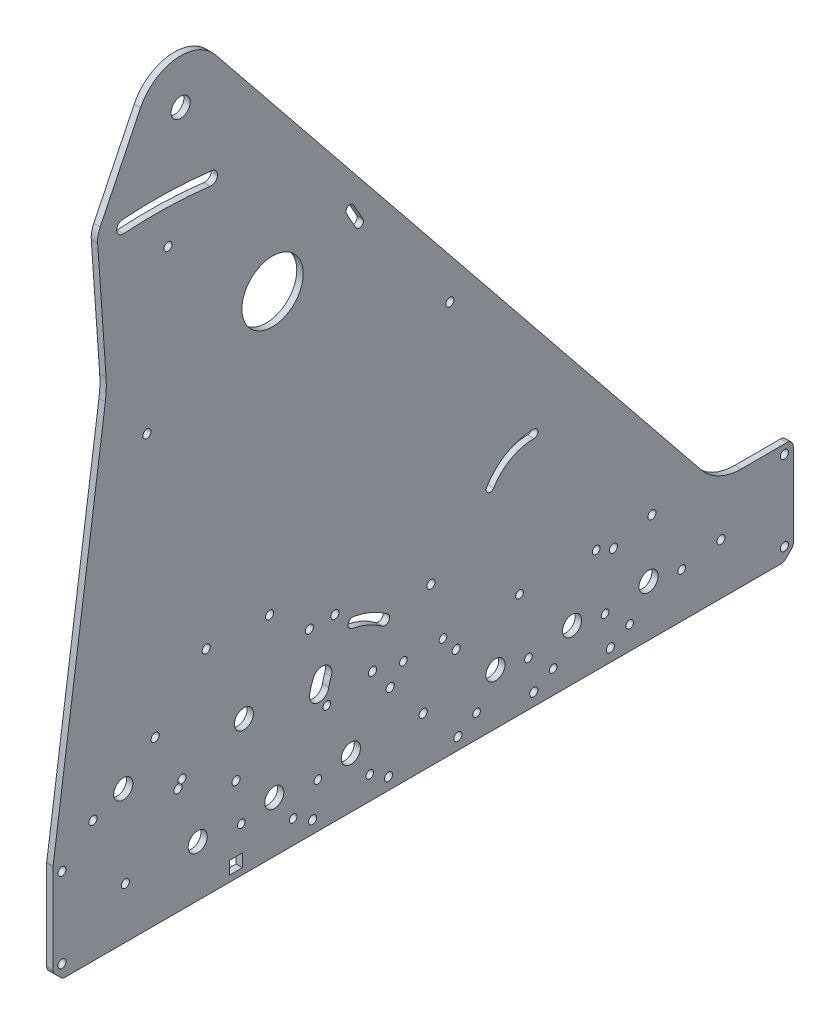
SolidWorks part; units mm, degrees
ref_plane "Front Plane" through (0, 0, 0) normal (0, 0, 1) x (1, 0, 0)
ref_plane "Top Plane" through (0, 0, 0) normal (0, 1, 0) x (1, 0, 0)
ref_plane "Right Plane" through (0, 0, 0) normal (1, 0, 0) x (0, 0, -1)
sketch "Sketch1" plane through (0, 0, 0) normal (1, 0, 0) x (0, 0, -1)
  line L0 (-184.15, -24.6062) -> (184.15, -24.6062)
  line L1 (184.15, -24.6062) -> (184.15, 26.1938)
  line L2 (184.15, 26.1938) -> (146.05, 26.1937)
  line L5 (-142.6632, 324.5299) -> (-184.15, 26.1938)
  line L6 (-184.15, 26.1938) -> (-184.15, -24.6062)
  line L7 (-184.15, 350.0437) -> (184.15, 350.0437) construction
  line L9 (146.05, 26.1937) -> (-103.3504, 335.4213)
  arc A0 (-103.3504, 335.4213) -> (-142.6632, 324.5299) centre (-120.65, 321.4687) ccw
  point P8 (0, -24.6062)
  dimension "D1" = 368.3
  dimension "D7" = 44.45
  dimension "D2" = 50.8
  dimension "D3" = 38.1
  dimension "D4" = 24.6062
  dimension "D5" = 374.65
  dimension "D6" = 304.8
  dimension "D8" = 346.075
extrude "Boss-Extrude1" add sketch "Sketch1" along normal blind 3.175
chamfer "Chamfer1" distance 4.7625 angle 45 2 edges at (1.5875, -24.6062, 184.15) (1.5875, -24.6062, -184.15)
fillet "Fillet1" radius 25.4 1 edges at (1.5875, 26.1937, -146.05)
fillet "Fillet2" radius 3.175 2 edges at (1.5875, 26.1938, 184.15) (1.5875, 26.1938, -184.15)
fillet "Fillet3" radius 3.175 4 edges at (1.5875, -19.8438, -184.15) (1.5875, -24.6062, -179.3875) (1.5875, -19.8437, 184.15) (1.5875, -24.6062, 179.3875)
sketch "Sketch30" plane through (3.175, 0, 0) normal (1, 0, 0) x (0, 0, -1)
  circle A8 centre (-89.211, 42.2593) radius 4.7625
  circle A9 centre (-25.1593, 30.6938) radius 2.032
  arc A10 (-51.7173, 35.4892) -> (-50.2741, 40.5715) centre (-25.1593, 30.6938) cw construction
  arc A11 (-54.7652, 42.3379) -> (-56.4665, 36.3468) centre (-25.1593, 30.6938) ccw
  arc A12 (-45.783, 38.8051) -> (-46.9681, 34.6317) centre (-25.1593, 30.6938) ccw
  arc A13 (-45.783, 38.8051) -> (-54.7652, 42.3379) centre (-50.2741, 40.5715) ccw
  arc A14 (-56.4665, 36.3468) -> (-46.9681, 34.6317) centre (-51.7173, 35.4892) ccw
  arc A15 (-34.9881, 56.6661) -> (-19.1131, 49.8125) centre (-41.7582, 19.1724) cw construction
  arc A16 (-17.6789, 51.753) -> (-34.5594, 59.0407) centre (-41.7582, 19.1724) ccw
  arc A17 (-20.5473, 47.8719) -> (-35.4169, 54.2915) centre (-41.7582, 19.1724) ccw
  arc A18 (-20.5473, 47.8719) -> (-17.6789, 51.753) centre (-19.1131, 49.8125) ccw
  arc A19 (-34.5594, 59.0407) -> (-35.4169, 54.2915) centre (-34.9881, 56.6661) ccw
  arc A20 (-19.1131, 49.8125) -> (-34.9881, 56.6661) centre (-41.7582, 19.1724) ccw construction
  circle A21 centre (94.6345, 23.8125) radius 2.032
  circle A22 centre (-56.6241, 64.5541) radius 2.032
  circle A23 centre (-43.9241, 64.5541) radius 2.032
  circle A24 centre (-56.6241, 64.5541) radius 1.905 construction
  circle A25 centre (-43.9241, 64.5541) radius 1.905 construction
  point P7 (-51.1204, 38.0658)
  point P19 (-26.6567, 54.1518)
  dimension "D2" = 9.652
  dimension "D4" = 4.064
  dimension "D1" = 4.064
  dimension ".375" = 9.525
  dimension "D3" = 4.826
extrude "Cut-Extrude9" cut sketch "Sketch30" against normal through all
sketch "Sketch16" plane through (3.175, 0, 0) normal (1, 0, 0) x (0, 0, -1)
  circle A0 centre (112.1746, 0.7937) radius 4.7625
  circle A1 centre (74.0746, 0.7937) radius 4.7625
  circle A2 centre (35.9746, 0.7937) radius 4.7625
  circle A3 centre (-35.9746, 0.7938) radius 4.7625
  circle A4 centre (-74.0746, 0.7938) radius 4.7625
  circle A5 centre (-112.1746, 0.7937) radius 4.7625
  dimension "D1" = 9.525
  dimension "D2" = 9.525
extrude "Cut-Extrude1" cut sketch "Sketch16" against normal up to next
sketch "Sketch25" plane through (3.175, 0, 0) normal (1, 0, 0) x (0, 0, -1)
  circle A0 centre (102.7672, -13.0003) radius 1.905 construction
  circle A1 centre (86.0486, 27.3622) radius 1.905 construction
  circle A2 centre (128.5804, -2.3081) radius 1.905 construction
  circle A3 centre (102.7672, -13.0003) radius 1.905
  circle A4 centre (86.0486, 27.3622) radius 1.905
  circle A5 centre (128.5804, -2.3081) radius 1.905
  circle A6 centre (64.6672, -13.0003) radius 1.905 construction
  circle A8 centre (-9.8486, 27.3622) radius 1.905 construction
  circle A10 centre (-47.9486, 27.3622) radius 1.905 construction
  circle A11 centre (-90.4804, -2.3081) radius 1.905 construction
  circle A12 centre (-64.6672, -13.0003) radius 1.905 construction
  circle A14 centre (-52.3804, -2.3081) radius 1.905 construction
  circle A15 centre (-26.5672, -13.0003) radius 1.905 construction
  circle A16 centre (9.8486, 27.3622) radius 1.905 construction
  circle A17 centre (26.5672, -13.0003) radius 1.905 construction
  circle A18 centre (47.9486, 27.3622) radius 1.905 construction
  circle A19 centre (52.3804, -2.3081) radius 1.905 construction
  circle A20 centre (90.4804, -2.3081) radius 1.905 construction
  circle A21 centre (-9.8486, 27.3622) radius 1.905
  circle A23 centre (-47.9486, 27.3622) radius 1.905
  circle A24 centre (-90.4804, -2.3081) radius 1.905
  circle A25 centre (-64.6672, -13.0003) radius 1.905
  circle A27 centre (-52.3804, -2.3081) radius 1.905
  circle A28 centre (-26.5672, -13.0003) radius 1.905
  circle A29 centre (9.8486, 27.3622) radius 1.905
  circle A30 centre (26.5672, -13.0003) radius 1.905
  circle A31 centre (47.9486, 27.3622) radius 1.905
  circle A32 centre (64.6672, -13.0003) radius 1.905
  circle A33 centre (52.3804, -2.3081) radius 1.905
  circle A34 centre (90.4804, -2.3081) radius 1.905
extrude "Cut-Extrude4" cut sketch "Sketch25" against normal up to next
sketch "Sketch23" plane through (3.175, 0, 0) normal (1, 0, 0) x (0, 0, -1)
  circle A0 centre (179.705, 21.7488) radius 1.905 construction
  point P0 (-55.0246, -18.3223)
  point P6 (-93.1246, 17.5943)
  point P9 (-17.2515, -18.6426)
  point P12 (-16.4124, 19.3854)
  point P15 (16.4124, 19.3854)
  point P18 (17.2515, -18.6426)
  point P21 (55.0246, -18.3223)
  point P35 (3.8736, 53.6853)
  point P38 (113.7728, 28.6594)
  point P44 (-179.705, 21.7487)
  point P47 (-179.705, -18.0026)
  point P50 (179.705, 21.7488)
  point P53 (179.705, -18.0026)
  point P59 (93.1246, -18.3223)
  point P63 (-122.0103, 28.5049)
  point P66 (-164.29, 36.0603)
hole_wizard "#8 (0.16) Diameter Hole1" positions "Sketch23" profile "Sketch24" hole size "#8" standard "ANSI Inch" end condition up to next
sketch "Sketch24" plane through (3.175, -18.3223, 55.0246) normal (0, 1, 0) x (0, 0, -1)
  line L0 (0, 0) -> (0, 3.175)
  line L1 (0, 3.175) -> (2.032, 3.175)
  line L2 (2.032, 3.175) -> (2.032, 0)
  line L5 (2.032, 0) -> (0, 0)
  line L11 (0, -6.35) -> (0, 107.95) construction
  dimension "Thru Hole Dia." = 4.064
  dimension "Thru Hole Depth" = 3.175
sketch "Sketch22" plane through (3.175, 0, 0) normal (1, 0, 0) x (0, 0, -1)
  line L0 (-96.2996, -15.1473) -> (-89.9496, -15.1473) construction
  line L1 (-96.2996, -15.1473) -> (-89.9496, -15.1473)
  line L2 (-96.2996, -15.1473) -> (-96.2996, -21.4973)
  line L3 (-96.2996, -21.4973) -> (-89.9496, -21.4973)
  line L4 (-89.9496, -15.1473) -> (-89.9496, -21.4973)
  line L5 (-96.2996, -15.1473) -> (-89.9496, -21.4973) construction
  line L6 (-96.2996, -21.4973) -> (-89.9496, -15.1473) construction
  line L7 (-89.9496, -15.1473) -> (-89.9496, -19.8734) construction
  point P0 (-93.1246, -18.3223)
  dimension "D1" = 6.35
extrude "Cut-Extrude3" cut sketch "Sketch22" against normal up to next
sketch "Sketch21" plane through (3.175, 0, 0) normal (1, 0, 0) x (0, 0, -1)
  circle A0 centre (-148.1579, 0.7937) radius 2.032
  circle A2 centre (0, 0) radius 2.032
  circle A3 centre (148.1579, 0.7938) radius 2.032
  dimension "D1" = 4.064
extrude "Cut-Extrude2" cut sketch "Sketch21" against normal up to next
sketch "Sketch26" [suppressed] plane through (3.175, 0, 0) normal (1, 0, 0) x (0, 0, -1)
  line L0 (-145.839, 321.5609) -> (-184.1236, 26.3971) construction
  line L1 (-178.0724, -24.6062) -> (178.0724, -24.6062) construction
  circle A0 centre (-121.0218, 216.6937) radius 15.24
  dimension "D1" = 30.48
  dimension "D2" = 38.1
  dimension "D3" = 241.3
extrude "Cut-Extrude5" [suppressed] cut sketch "Sketch26" against normal through all
sketch "Sketch27" plane through (3.175, 0, 0) normal (1, 0, 0) x (0, 0, -1)
  circle A0 centre (-120.65, 321.4687) radius 4.7625
  dimension "D1" = 9.525
extrude "Cut-Extrude6" cut sketch "Sketch27" against normal through all
sketch "Sketch28" plane through (3.175, 0, 0) normal (1, 0, 0) x (0, 0, -1)
  line L0 (-120.65, 321.4687) -> (-103.9389, 280.2796) construction
  line L1 (-103.9389, 280.2796) -> (-86.9156, 261.4285) construction
  line L2 (-86.9156, 261.4285) -> (-90.8226, 249.3444) construction
  line L3 (-90.8226, 249.3444) -> (-94.7296, 237.2603) construction
  line L4 (-142.6632, 324.5299) -> (-184.1197, 26.4114) construction
  circle A0 centre (-94.7296, 237.2603) radius 2.032
  circle A1 centre (-90.8226, 249.3444) radius 2.032
  circle A2 centre (-86.9156, 261.4285) radius 2.0955
  circle A3 centre (-103.9389, 280.2796) radius 2.032
  dimension "D4" = 4.064
  dimension "D5" = 4.191
  dimension "D6" = 4.064
  dimension "D1" = 25.4
  dimension "D2" = 44.45
  dimension "D3" = 12.7
  dimension "D7" = 30
  dimension "D8" = 120
  dimension "D9" = 160
extrude "Cut-Extrude7" [suppressed] cut sketch "Sketch28" against normal through all
sketch "Sketch31" plane through (0, 0, 0) normal (-1, 0, 0) x (0, 0, 1)
extrude "Cut-Extrude10" [suppressed] cut sketch "Sketch31" against normal through all
sketch "Sketch34" plane through (0, 0, 0) normal (-1, 0, 0) x (0, 0, 1)
  line L3 (123.2042, 95.6381) -> (126.7027, 70.4802) construction
  line L4 (125.3426, 95.9355) -> (128.8411, 70.7775)
  line L5 (121.0658, 95.3407) -> (124.5642, 70.1828)
  line L6 (142.6632, 324.5299) -> (184.1197, 26.4114) construction
  arc A2 (125.3426, 95.9355) -> (121.0658, 95.3407) centre (123.2042, 95.6381) ccw
  arc A3 (124.5642, 70.1828) -> (128.8411, 70.7775) centre (126.7027, 70.4802) ccw
  point P9 (124.9534, 83.0591)
  dimension "D8" = 4.318
  dimension "D6" = 50.8
  dimension "D7" = 25.4
extrude "Cut-Extrude12" [suppressed] cut sketch "Sketch34" against normal through all
sketch "Sketch38" plane through (3.175, 0, 0) normal (1, 0, 0) x (0, 0, -1)
  line L0 (-184.15, 25.974) -> (-184.15, -18.5286) construction
  line L1 (-178.0724, -24.6062) -> (178.0724, -24.6062) construction
  circle A0 centre (-133.35, 56.3562) radius 2.032
  circle A1 centre (-149.225, 42.0687) radius 4.7625
  circle A2 centre (-107.95, 81.7563) radius 2.032
  dimension "D1" = 50.8
  dimension "D3" = 4.064
  dimension "D4" = 9.525
  dimension "D7" = 4.064
  dimension "D2" = 80.9625
  dimension "D5" = 15.875
  dimension "D6" = 14.2875
  dimension "D8" = 25.4
  dimension "D9" = 25.4
extrude "Cut-Extrude14" cut sketch "Sketch38" against normal through all
sketch "Sketch56" plane through (3.175, 0, 0) normal (1, 0, 0) x (0, 0, -1)
  line L0 (-133.35, 284.9563) -> (-133.35, 56.3562) construction
  line L1 (-149.2963, 284.3994) -> (-133.35, 56.3562) construction
  line L2 (-133.35, 56.3562) -> (-105.4907, 283.2523) construction
  arc A0 (-149.2963, 284.3994) -> (-105.4907, 283.2523) centre (-133.35, 56.3562) cw
  arc A1 (-142.7671, 191.0274) -> (-116.8976, 190.35) centre (-133.35, 56.3562) cw
  dimension "D1" = 4
  dimension "D3" = 228.6
  dimension "D4" = 135
  dimension "D2" = 7
sketch "Sketch54" plane through (3.175, 0, 0) normal (1, 0, 0) x (0, 0, -1)
  line L0 (-142.6632, 324.5299) -> (-184.1197, 26.4114) construction
  line L1 (-140.6316, 331.1994) -> (-160.7144, 289.9597)
  line L2 (-142.6632, 324.5299) -> (-157.4154, 218.4453)
  line L3 (-140.6316, 331.1994) -> (-217.348, 331.1994) construction
  line L4 (-149.2963, 284.3994) -> (-133.35, 56.3562) construction
  line L5 (-161.9654, 283.5135) -> (-157.4154, 218.4453)
  arc A1 (-103.3504, 335.4213) -> (-142.6632, 324.5299) centre (-120.65, 321.4687) ccw construction
  arc A2 (-160.7144, 289.9597) -> (-161.9654, 283.5135) centre (-149.2963, 284.3994) ccw
  arc A3 (-140.6316, 331.1994) -> (-142.6632, 324.5299) centre (-120.65, 321.4687) ccw
  dimension "D1" = 12.7
extrude "Boss-Extrude2" add sketch "Sketch54" against normal up to surface (3.175 mm away) up to face at (0, 81.7563, 105.918)
sketch "Sketch57" plane through (3.175, 0, 0) normal (1, 0, 0) x (0, 0, -1)
  line L0 (138.4249, 35.6479) -> (-103.3504, 335.4213) construction
  arc A0 (-149.2963, 284.3994) -> (-105.4907, 283.2523) centre (-133.35, 56.3562) cw construction
  arc A1 (-105.1037, 286.4036) -> (-149.5178, 287.5667) centre (-133.35, 56.3562) ccw
  arc A2 (-105.8776, 280.101) -> (-149.0749, 281.2321) centre (-133.35, 56.3562) ccw
  arc A3 (-105.8776, 280.101) -> (-105.1037, 286.4036) centre (-105.4907, 283.2523) ccw
  arc A4 (-149.5178, 287.5667) -> (-149.0749, 281.2321) centre (-149.2963, 284.3994) ccw
  arc A5 (-105.4907, 283.2523) -> (-149.2963, 284.3994) centre (-133.35, 56.3562) ccw construction
  arc A6 (-142.7671, 191.0274) -> (-116.8976, 190.35) centre (-133.35, 56.3562) cw construction
  arc A7 (-116.5107, 193.5013) -> (-142.9886, 194.1947) centre (-133.35, 56.3562) ccw construction
  arc A8 (-117.2846, 187.1986) -> (-142.5456, 187.8601) centre (-133.35, 56.3562) ccw construction
  arc A9 (-117.2846, 187.1986) -> (-116.5107, 193.5013) centre (-116.8976, 190.35) ccw construction
  arc A10 (-142.9886, 194.1947) -> (-142.5456, 187.8601) centre (-142.7671, 191.0274) ccw construction
  circle A11 centre (13.2774, 170.5867) radius 2.032
  point P3 (-127.3659, 284.8779)
  point P16 (-129.8161, 191.31)
  dimension "D1" = 6.35
  dimension "D2" = 4.064
  dimension "D3" = 12.7
  dimension "D4" = 130.175
extrude "Cut-Extrude26" cut sketch "Sketch57" against normal up to next
sketch "Sketch37" plane through (3.175, 0, 0) normal (1, 0, 0) x (0, 0, -1)
  line L0 (55.0742, 92.9044) -> (63.2984, 92.9044) construction
  arc A1 (33.3375, 80.645) -> (55.0742, 92.9044) centre (55.0742, 67.5044) cw construction
  arc A2 (55.0742, 94.9364) -> (31.5986, 81.6962) centre (55.0742, 67.5044) ccw
  arc A3 (55.0742, 90.8724) -> (35.0764, 79.5938) centre (55.0742, 67.5044) ccw
  arc A4 (55.0742, 90.8724) -> (55.0742, 94.9364) centre (55.0742, 92.9044) ccw
  arc A5 (31.5986, 81.6962) -> (35.0764, 79.5938) centre (33.3375, 80.645) ccw
  circle A8 centre (0, 0) radius 2.032 construction
  point P4 (42.5965, 89.6283)
  dimension "D1" = 25.4
  dimension "D4" = 24.9555
  dimension "D5" = 2.032
  dimension "D2" = 33.3375
  dimension "D3" = 80.645
extrude "Cut-Extrude13" cut sketch "Sketch37" against normal through all
sketch "Sketch40" plane through (3.175, 0, 0) normal (1, 0, 0) x (0, 0, -1)
  circle A0 centre (-120.015, 31.75) radius 2.032
  dimension "D1" = 4.064
  dimension "D2" = 120.015
  dimension "D3" = 31.75
extrude "Cut-Extrude16" cut sketch "Sketch40" against normal through all
sketch "Sketch41" [suppressed] plane through (3.175, 0, 0) normal (1, 0, 0) x (0, 0, -1)
  line L0 (-120.65, 318.2937) -> (-98.425, 279.7989) construction
  line L1 (-98.425, 279.7989) -> (-77.6666, 265.1617) construction
  line L2 (-120.65, 318.2937) -> (-60.41, 318.2937) construction
  circle A0 centre (-120.65, 318.2937) radius 25.4 construction
  circle A1 centre (-98.425, 279.7989) radius 19.05 construction
  circle A2 centre (-77.6666, 265.1617) radius 6.35 construction
  circle A3 centre (-98.425, 279.7989) radius 2.032
  circle A4 centre (-77.6666, 265.1617) radius 2.032
  dimension "D1" = 50.8
  dimension "D2" = 38.1
  dimension "D3" = 12.7
  dimension "D4" = 4.064
  dimension "D5" = 60
extrude "Cut-Extrude17" [suppressed] cut sketch "Sketch41" against normal through all
sketch "Sketch43" plane through (3.175, 0, 0) normal (1, 0, 0) x (0, 0, -1)
  line L0 (-152.4, 200.025) -> (-123.6487, 200.025) construction
  line L1 (-115.9779, 252.0412) -> (-152.4, 200.025) construction
  circle A0 centre (-152.4, 200.025) radius 2.032
  arc A1 (-143.2813, 262.8669) -> (-96.4668, 230.087) centre (-152.4, 200.025) cw construction
  arc A2 (-92.2158, 232.3717) -> (-142.5883, 267.6428) centre (-152.4, 200.025) ccw
  arc A3 (-100.7177, 227.8023) -> (-143.9743, 258.0909) centre (-152.4, 200.025) ccw
  arc A4 (-100.7177, 227.8023) -> (-92.2158, 232.3717) centre (-96.4668, 230.087) ccw
  arc A5 (-142.5883, 267.6428) -> (-143.9743, 258.0909) centre (-143.2813, 262.8669) ccw
  point P6 (-115.9779, 252.0412)
  dimension "D1" = 4.064
  dimension "D4" = 4.826
  dimension "D2" = 200.025
  dimension "D3" = 152.4
  dimension "D5" = 63.5
  dimension "D6" = 57.15
  dimension "D7" = 55
extrude "Cut-Extrude19" [suppressed] cut sketch "Sketch43" against normal through all
sketch "Sketch44" plane through (3.175, 0, 0) normal (1, 0, 0) x (0, 0, -1)
  circle A0 centre (-142.875, 226.3775) radius 2.032
  dimension "D1" = 4.064
  dimension "D2" = 142.875
  dimension "D3" = 226.3775
extrude "Cut-Extrude20" [suppressed] cut sketch "Sketch44" against normal through all
sketch "Sketch50" plane through (0, 0, 0) normal (-1, 0, 0) x (0, 0, 1)
  line L0 (89.6567, 207.1688) -> (64.2567, 207.1688) construction
  line L1 (89.6567, 205.1368) -> (64.2567, 205.1368)
  line L2 (89.6567, 209.2008) -> (64.2567, 209.2008)
  line L3 (64.2567, 194.4688) -> (38.8567, 194.4688) construction
  line L4 (64.2567, 192.4368) -> (38.8567, 192.4368)
  line L5 (64.2567, 196.5008) -> (38.8567, 196.5008)
  arc A1 (89.6567, 205.1368) -> (89.6567, 209.2008) centre (89.6567, 207.1688) ccw
  arc A2 (64.2567, 209.2008) -> (64.2567, 205.1368) centre (64.2567, 207.1688) ccw
  arc A3 (64.2567, 192.4368) -> (64.2567, 196.5008) centre (64.2567, 194.4688) ccw
  arc A4 (38.8567, 196.5008) -> (38.8567, 192.4368) centre (38.8567, 194.4688) ccw
  point P3 (76.9567, 207.1688)
  point P5 (51.5567, 194.4688)
  dimension "D1" = 2.032
  dimension "D2" = 207.1688
  dimension "D3" = 89.6567
  dimension "D4" = 25.4
  dimension "D5" = 12.7
extrude "Cut-Extrude22" [suppressed] cut sketch "Sketch50" against normal through all
sketch "Sketch51" plane through (3.175, 0, 0) normal (1, 0, 0) x (0, 0, -1)
  circle A0 centre (-111.125, 222.6469) radius 2.032
  circle A1 centre (-111.125, 190.8969) radius 2.032
  dimension "D1" = 222.6469
  dimension "D3" = 31.75
  dimension "D4" = 4.064
  dimension "D2" = 111.125
extrude "Cut-Extrude23" [suppressed] cut sketch "Sketch51" against normal through all
sketch "Sketch52" [suppressed] plane through (0, 0, 0) normal (-1, 0, 0) x (0, 0, 1)
  line L0 (145.839, 321.5609) -> (184.1236, 26.3971) construction
  line L1 (142.875, 226.3775) -> (142.0856, 251.7652) construction
  line L2 (120.4939, 238.3877) -> (142.875, 226.3775) construction
  arc A5 (142.0856, 251.7652) -> (120.4939, 238.3877) centre (142.875, 226.3775) ccw construction
  arc A6 (142.0224, 253.7962) -> (118.7034, 239.3485) centre (142.875, 226.3775) ccw
  arc A7 (142.1487, 249.7342) -> (122.2844, 237.4269) centre (142.875, 226.3775) ccw
  arc A8 (142.1487, 249.7342) -> (142.0224, 253.7962) centre (142.0856, 251.7652) ccw
  arc A9 (118.7034, 239.3485) -> (122.2844, 237.4269) centre (120.4939, 238.3877) ccw
  point P4 (129.4975, 247.9692)
  dimension "D1" = 25.4
  dimension "D2" = 2.032
  dimension "D3" = 12.7
  dimension "D4" = 60
extrude "Cut-Extrude24" [suppressed] cut sketch "Sketch52" against normal through all
sketch "Sketch53" plane through (3.175, 0, 0) normal (1, 0, 0) x (0, 0, -1)
  line L0 (-25.4, 197.2663) -> (-25.4, 135.876) construction
  line L1 (-23.368, 197.2663) -> (-23.368, 135.876)
  line L2 (-27.432, 197.2663) -> (-27.432, 135.876)
  arc A0 (-23.368, 197.2663) -> (-27.432, 197.2663) centre (-25.4, 197.2663) ccw
  arc A1 (-27.432, 135.876) -> (-23.368, 135.876) centre (-25.4, 135.876) ccw
  point P2 (-25.4, 166.5712)
  dimension "D1" = 2.032
  dimension "D2" = 61.3903
  dimension "D3" = 197.2663
  dimension "D4" = 25.4
extrude "Cut-Extrude25" [suppressed] cut sketch "Sketch53" against normal through all
sketch "Sketch58" plane through (3.175, 0, 0) normal (1, 0, 0) x (0, 0, -1)
  line L0 (138.4249, 35.6479) -> (-103.3504, 335.4213) construction
  line L1 (-74.9571, 219.298) -> (-112.7732, 223.9412) construction
  line L2 (-133.35, 56.3562) -> (-105.4907, 283.2523) construction
  circle A0 centre (-74.9571, 219.298) radius 15.24
  dimension "D1" = 50.8
  dimension "D2" = 30.48
  dimension "D3" = 38.1
extrude "Cut-Extrude27" cut sketch "Sketch58" against normal through all
sketch "Sketch60" [suppressed] plane through (0, 0, 0) normal (-1, 0, 0) x (0, 0, 1)
  line L1 (-37.547, 154.5028) -> (64.3989, 263.8478) construction
  line L2 (120.65, 321.4687) -> (120.65, 283.4951) construction
  line L3 (-17.6374, 138.8786) -> (63.8163, 263.1055) construction
  line L4 (113.0282, 299.2883) -> (107.0925, 303.8578) construction
  line L5 (65.8258, 264.9495) -> (112.2759, 289.9949) construction
  line L7 (120.65, 321.4687) -> (120.65, 359.4144) construction
  line L8 (120.65, 321.4687) -> (109.6389, 294.8856) construction
  line L10 (120.65, 321.4687) -> (-169.232, 227.2804) construction
  line L11 (120.65, 321.4687) -> (354.1403, 125.5471) construction
  line L12 (64.8747, 264.3011) -> (106.0507, 299.1279) construction
  line L13 (110.3554, 300.3954) -> (117.7837, 299.4293) construction
  line L14 (-16.0993, 160.9177) -> (-13.2774, 170.5867) construction
  circle A7 centre (74.9571, 219.298) radius 33.3375 construction
  circle A10 centre (68.4628, 260.0588) radius 2.032
  circle A11 centre (68.4628, 260.0588) radius 7.9375 construction
  circle A15 centre (-28.258, 145.8423) radius 1.778
  circle A17 centre (120.65, 321.4687) radius 22.225 construction
  circle A20 centre (109.6389, 294.8856) radius 6.5484 construction
  circle A21 centre (109.6389, 294.8856) radius 2.032
  circle A22 centre (109.6389, 294.8856) radius 5.5563 construction
  circle A23 centre (68.4628, 260.0588) radius 5.5563 construction
  circle A24 centre (-28.258, 145.8423) radius 12.7 construction
  arc A25 (-44.7806, 147.1408) -> (-23.4901, 129.9695) centre (-28.258, 145.8423) ccw construction
  circle A26 centre (-16.0993, 160.9177) radius 2.032
  circle A27 centre (-35.0103, 118.6566) radius 2.032
  circle A28 centre (-53.3973, 133.4862) radius 2.032
  circle A31 centre (-16.0993, 160.9177) radius 1.905 construction
  circle A32 centre (-35.0103, 118.6566) radius 1.905 construction
  circle A33 centre (-53.3973, 133.4862) radius 1.905 construction
  dimension "D4" = 11.1125
  dimension "D3" = 13.0969
  dimension "D6" = 66.675
  dimension "D7" = 4.064
  dimension "D8" = 4.064
  dimension "D2" = 22.5
  dimension "D9" = 15.875
  dimension "D5" = 44.45
  dimension "D15" = 25.4
  dimension "D10" = 3.556
  dimension "D11" = 108
  dimension "D12" = 130
  dimension "D13" = 304.8
  dimension "D14" = 304.8
extrude "Cut-Extrude28" [suppressed] cut sketch "Sketch60" against normal through all
fillet "Fillet4" radius 50.8 1 edges at (1.5875, 218.4453, 157.4154)
sketch "Sketch62" plane through (0, 0, 0) normal (-1, 0, 0) x (0, 0, 1)
  line L3 (31.75, 227.0125) -> (36.3514, 235.3523) construction
  line L4 (29.9708, 227.9941) -> (34.5722, 236.334)
  line L5 (33.5292, 226.0309) -> (38.1306, 234.3707)
  line L6 (-138.4249, 35.6479) -> (103.3504, 335.4213) construction
  arc A6 (29.9708, 227.9941) -> (33.5292, 226.0309) centre (31.75, 227.0125) ccw
  arc A7 (38.1306, 234.3707) -> (34.5722, 236.334) centre (36.3514, 235.3523) ccw
  point P3 (34.0507, 231.1824)
  dimension "D1" = 31.75
  dimension "D3" = 9.525
  dimension "D4" = 2.032
  dimension "D2" = 227.0125
  dimension "D5" = 10
extrude "Cut-Extrude30" cut sketch "Sketch62" against normal through all
sketch "Sketch63" plane through (3.175, 0, 0) normal (1, 0, 0) x (0, 0, -1)
  circle A0 centre (-76.4451, 80.645) radius 2.032
  dimension "D1" = 4.064
  dimension "D2" = 80.645
  dimension "D3" = 76.4451
extrude "Cut-Extrude31" cut sketch "Sketch63" against normal through all
sketch "Sketch64" [suppressed] plane through (0, 0, 0) normal (-1, 0, 0) x (0, 0, 1)
  circle A0 centre (60.4309, 266.5368) radius 2.032
  circle A1 centre (60.4309, 266.5368) radius 1.905 construction
  circle A2 centre (78.1747, 256.5724) radius 2.032
  circle A3 centre (119.5608, 294.8856) radius 2.032
  circle A4 centre (78.1747, 256.5724) radius 1.905 construction
  circle A5 centre (119.5608, 294.8856) radius 1.905 construction
  dimension "D1" = 4.064
extrude "Cut-Extrude32" [suppressed] cut sketch "Sketch64" against normal up to next
sketch "Sketch65" plane through (3.175, 0, 0) normal (1, 0, 0) x (0, 0, -1)
  circle A0 centre (-126.9492, 264.6448) radius 2.032
  circle A1 centre (-137.4446, 189.171) radius 2.032
  circle A2 centre (-126.9492, 264.6448) radius 2.032 construction
  circle A3 centre (-137.4446, 189.171) radius 2.032 construction
  dimension "D1" = 4.064
extrude "Cut-Extrude33" cut sketch "Sketch65" against normal through all
